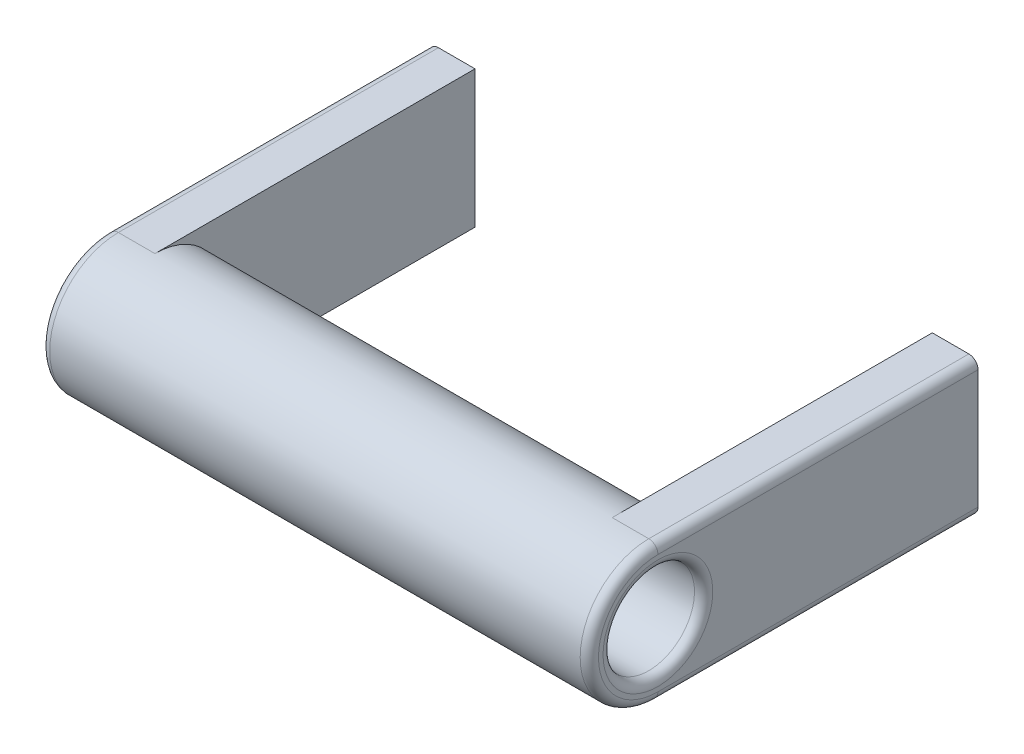
SolidWorks part; units mm, degrees
ref_plane "Спереди" through (0, 0, 0) normal (0, 0, 1) x (1, 0, 0)
ref_plane "Сверху" through (0, 0, 0) normal (0, 1, 0) x (1, 0, 0)
ref_plane "Справа" through (0, 0, 0) normal (1, 0, 0) x (0, 0, -1)
other "Configuration Table"
sketch "Sketch1" plane through (0, 0, 0) normal (0, 0, 1) x (1, 0, 0)
  line L0 (0, 0) -> (0, 51.5979) construction
  line L1 (60, -15) -> (50, -15)
  line L2 (60, -15) -> (60, 15)
  line L3 (60, 15) -> (50, 15)
  line L4 (50, -15) -> (50, 15)
  line L5 (60, -15) -> (50, 15) construction
  line L6 (60, 15) -> (50, -15) construction
  line L7 (0, 0) -> (55, 0) construction
  line L8 (-60, 15) -> (-50, 15)
  line L9 (-50, -15) -> (-50, 15)
  line L10 (-60, -15) -> (-50, -15)
  line L11 (-60, -15) -> (-60, 15)
  point P0 (55, 0)
  point P13 (-55, 15)
  dimension "D1" = 110
  dimension "D2" = 10
  dimension "D3" = 30
extrude "Boss-Extrude1" add sketch "Sketch1" along normal blind 70
sketch "Sketch2" plane through (60, 0, 0) normal (1, 0, 0) x (0, 0, -1)
  line L0 (-70, -15) -> (-70, 15) construction
  line L1 (-70, -15) -> (0, -15) construction
  circle A0 centre (-70, 0) radius 15
  point P4 (-70, 0)
extrude "Boss-Extrude2" add sketch "Sketch2" against normal up to surface (120 mm away) up to face at (-60, 0, 35)
sketch "Sketch3" plane through (-60, 0, 0) normal (-1, 0, 0) x (0, 0, 1)
  line L0 (70, 15) -> (70, -15) construction
  line L1 (70, -15) -> (0, -15) construction
  arc A0 (70, -15) -> (70, 15) centre (70, 0) ccw construction
  circle A1 centre (70, 0) radius 10
  dimension "D1" = 5
extrude "Cut-Extrude1" cut sketch "Sketch3" against normal up to next and the other way through all
fillet "Fillet1" radius 2 8 edges at (-60, -15, 35) (-60, 0, 85) (60, -15, 35) (60, 0, 85) (-60, 10, 70) (-60, 15, 35) (60, 0, 80) (60, 15, 35)
sketch "Sketch4" plane through (0, 0, 0) normal (0, 0, -1) x (-1, 0, 0)
  line L0 (-50, 0) -> (-60, 0) construction
  line L1 (-50, 15) -> (-50, -15) construction
  line L2 (-60, -13) -> (-60, 13) construction
  line L3 (-55, 0) -> (-55, 12.211) construction
  line L4 (0, 0) -> (0, 44.7084) construction
  circle A0 centre (-55, 7) radius 1.5
  circle A1 centre (-55, -7) radius 1.5
  circle A2 centre (55, -7) radius 1.5
  circle A3 centre (55, 7) radius 1.5
  dimension "D1" = 3
  dimension "D2" = 14
extrude "Cut-Extrude2" cut sketch "Sketch4" against normal blind 15
